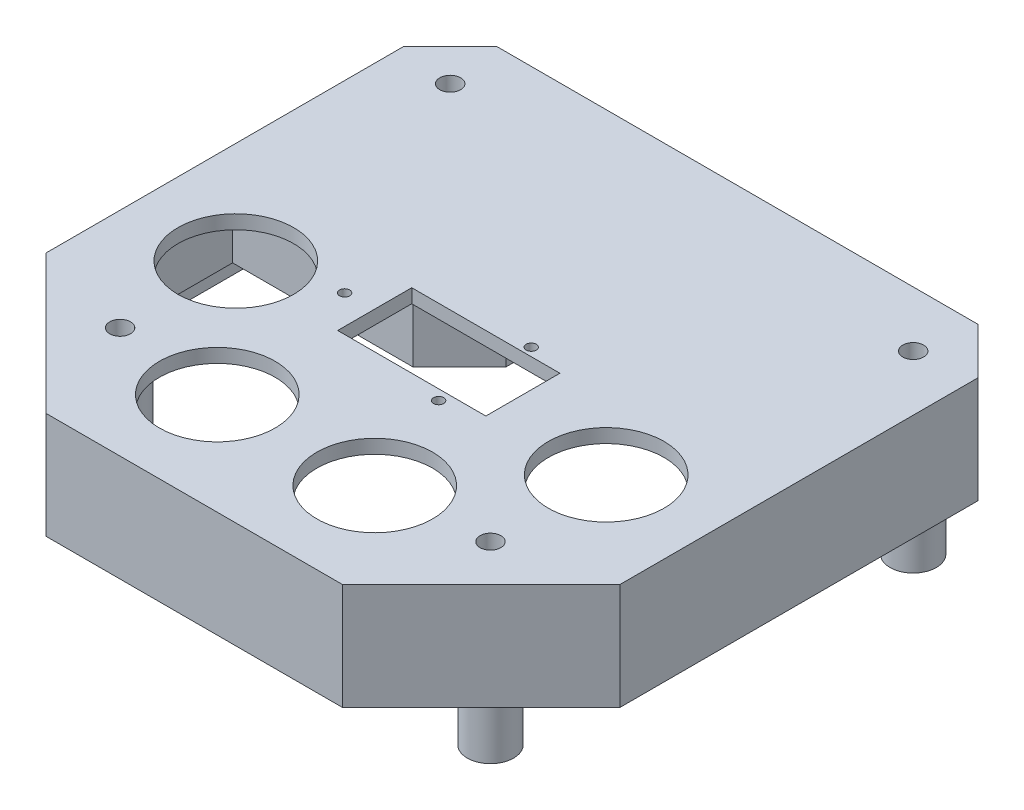
SolidWorks part; units mm, degrees
ref_plane "Plan de face" through (0, 0, 0) normal (0, 0, 1) x (1, 0, 0)
ref_plane "Plan de dessus" through (0, 0, 0) normal (0, 1, 0) x (1, 0, 0)
ref_plane "Plan de droite" through (0, 0, 0) normal (1, 0, 0) x (0, 0, -1)
sketch "Esquisse1" plane through (0, 0, 0) normal (0, 1, 0) x (1, 0, 0)
  line L0 (0, 0) -> (0, 64.9796) construction
  line L1 (-40, 27) -> (0, 27) construction
  line L2 (-17, 0) -> (0, 0) construction
  line L4 (62, -22) -> (-62, -22)
  line L5 (-16, 41) -> (16, 41)
  line L6 (-16, 41) -> (-16, 25)
  line L7 (-16, 25) -> (16, 25)
  line L8 (16, 41) -> (16, 25)
  line L9 (62, -22) -> (62, 95.3055)
  line L10 (62, 95.3055) -> (-62, 95.3055)
  line L11 (-62, -22) -> (-62, 95.3055)
  circle A0 centre (-40, 27) radius 12.5
  circle A1 centre (-17, 0) radius 12.5
  circle A2 centre (17, 0) radius 12.5
  circle A3 centre (40, 27) radius 12.5
  point P15 (0, 25)
  dimension "D1" = 25
  dimension "D2" = 16
  dimension "D3" = 32
  dimension "D4" = 17
  dimension "D5" = 25
  dimension "D6" = 27
  dimension "D7" = 40
  dimension "D8" = 22
  dimension "D9" = 22
  dimension "D10" = 22
sketch "Esquisse3" plane through (0, 0, 0) normal (0, 1, 0) x (1, 0, 0)
  line L0 (9.021, 32.7832) -> (18.021, 32.7832) construction
  line L1 (-22.279, 22.7832) -> (18.021, 22.7832)
  line L2 (-22.279, 22.7832) -> (-22.279, 42.7832)
  line L3 (-22.279, 42.7832) -> (18.021, 42.7832)
  line L4 (18.021, 22.7832) -> (18.021, 42.7832)
  line L5 (-15.079, 26.1832) -> (15.021, 26.1832)
  line L6 (-15.079, 26.1832) -> (-15.079, 40.2832)
  line L7 (-15.079, 40.2832) -> (15.021, 40.2832)
  line L8 (15.021, 26.1832) -> (15.021, 40.2832)
  line L9 (18.021, 38.8332) -> (9.021, 38.8332)
  line L10 (18.021, 38.8332) -> (18.021, 26.7332)
  line L11 (18.021, 26.7332) -> (9.021, 26.7332)
  line L12 (9.021, 38.8332) -> (9.021, 26.7332)
  line L13 (-18.279, 32.7832) -> (-22.279, 32.7832) construction
  line L14 (-9.079, 39.1832) -> (-18.279, 39.1832)
  line L15 (-9.079, 39.1832) -> (-9.079, 26.3832)
  line L16 (-9.079, 26.3832) -> (-18.279, 26.3832)
  line L17 (-18.279, 39.1832) -> (-18.279, 26.3832)
  circle A0 centre (18.021, 32.7832) radius 2.05
  circle A1 centre (8.021, 42.7832) radius 2.05
  circle A2 centre (8.021, 22.7832) radius 2.05
  circle A3 centre (-12.279, 22.7832) radius 2.05
  circle A4 centre (-12.279, 42.7832) radius 2.05
  circle A5 centre (-22.279, 32.7832) radius 2.05
  circle A6 centre (-22.279, 32.7832) radius 1.1
  circle A7 centre (8.021, 42.7832) radius 1.1
  circle A8 centre (8.021, 22.7832) radius 1.1
  dimension "D7" = 4.1
  dimension "D10" = 2.2
  dimension "D1" = 20
  dimension "D2" = 40.3
  dimension "D3" = 30.1
  dimension "D4" = 14.1
  dimension "D5" = 3
  dimension "D6" = 2.5
  dimension "D8" = 10
  dimension "D9" = 10
  dimension "D11" = 12.1
  dimension "D12" = 9
  dimension "D13" = 9.2
  dimension "D14" = 12.8
  dimension "D15" = 4
extrude "Boss.-Extru.1" add sketch "Esquisse1" along normal blind 3
extrude "Enlèv. mat.-Extru.1" cut sketch "Esquisse3" along normal through all contours L2 A6 | L2 A6 | L3 A7 | L3 A7 | L1 A8 | L1 A8 region at (8.021, 0, -22.3163) region at (8.021, 0, -23.25) region at (-22.7458, 0, -32.7832) region at (-21.8121, 0, -32.7832) region at (8.021, 0, -42.3163) region at (8.021, 0, -43.25)
chamfer "Chanfrein1" distance 30 angle 45 2 edges at (-62, 1.5, 22) (62, 1.5, 22)
chamfer "Chanfrein2" distance 10 angle 45 2 edges at (62, 1.5, -95.3055) (-62, 1.5, -95.3055)
sketch "Esquisse4" plane through (0, 0, 0) normal (0, 1, 0) x (1, 0, 0)
  line L0 (-62, 85.3055) -> (-62, 8) construction
  line L1 (52, 95.3055) -> (-52, 95.3055) construction
  line L2 (62, 8) -> (62, 85.3055) construction
  line L3 (-32, -22) -> (32, -22) construction
  circle A0 centre (-40, 2) radius 2.25
  circle A1 centre (-40, 2) radius 5
  circle A2 centre (40, 2) radius 2.25
  circle A3 centre (40, 2) radius 5
  circle A4 centre (50, 83.3055) radius 5
  circle A5 centre (50, 83.3055) radius 2.25
  circle A6 centre (-50, 83.3055) radius 2.25
  circle A7 centre (-50, 83.3055) radius 5
  dimension "D1" = 4.5
  dimension "D2" = 10
  dimension "D3" = 12
  dimension "D4" = 12
  dimension "D5" = 12
  dimension "D6" = 24
  dimension "D7" = 22
  dimension "D8" = 22
extrude "Enlèv. mat.-Extru.2" cut sketch "Esquisse4" along normal through all contours A6 | A5 | A2 | A0 region at (-40, 0, -2) region at (40, 0, -2) region at (50, 0, -83.3055) region at (-50, 0, -83.3055)
extrude "Boss.-Extru.2" add sketch "Esquisse4<3>" against normal blind 35
sketch "Esquisse4<3>" plane through (0, 0, 0) normal (0, 1, 0) x (1, 0, 0) same geometry as "Esquisse4"
sketch "Esquisse5" plane through (0, 0, 0) normal (0, 1, 0) x (1, 0, 0)
  line L0 (-62, 85.3055) -> (-52, 95.3055)
  line L1 (-52, 95.3055) -> (52, 95.3055)
  line L2 (52, 95.3055) -> (62, 85.3055)
  line L3 (62, 85.3055) -> (62, 8)
  line L4 (62, 8) -> (32, -22)
  line L5 (32, -22) -> (-32, -22)
  line L6 (-32, -22) -> (-62, 8)
  line L7 (-62, 8) -> (-62, 85.3055)
  line L8 (-58, 83.6486) -> (-50.3431, 91.3055)
  line L9 (-50.3431, 91.3055) -> (50.3431, 91.3055)
  line L10 (50.3431, 91.3055) -> (58, 83.6486)
  line L11 (58, 83.6486) -> (58, 9.6569)
  line L12 (58, 9.6569) -> (30.3431, -18)
  line L13 (30.3431, -18) -> (-30.3431, -18)
  line L14 (-30.3431, -18) -> (-58, 9.6569)
  line L15 (-58, 9.6569) -> (-58, 83.6486)
  line L16 (-60.7, 84.767) -> (-51.4615, 94.0055)
  line L17 (-51.4615, 94.0055) -> (51.4615, 94.0055)
  line L18 (51.4615, 94.0055) -> (60.1722, 85.2948)
  line L19 (60.1722, 85.2948) -> (60.1722, 8.0107)
  line L20 (60.1722, 8.0107) -> (31.4615, -20.7)
  line L21 (31.4615, -20.7) -> (-31.4615, -20.7)
  line L22 (-31.4615, -20.7) -> (-60.7, 8.5385)
  line L23 (-60.7, 8.5385) -> (-60.7, 84.767)
  point P28 (-46.0808, -6.0808)
  dimension "D1" = 4
  dimension "D2" = 4
  dimension "D3" = 4
  dimension "D4" = 4
  dimension "D5" = 4
  dimension "D6" = 4
  dimension "D7" = 4
  dimension "D8" = 4
  dimension "D9" = 1.3
  dimension "D10" = 1.3
  dimension "D11" = 1.3
  dimension "D12" = 1.3
  dimension "D13" = 1.8278
  dimension "D14" = 1.3
  dimension "D15" = 1.3
  dimension "D16" = 1.3
extrude "Boss.-Extru.3" add sketch "Esquisse5" against normal blind 20 contours L7 L6 L5 L4 L3 L2 L1 L0 L22 L23 L16 L17 L18 L19 L20 L21 region at (-56.8793, 0, -90.1848)
extrude "Boss.-Extru.4" add sketch "Esquisse5<3>" against normal blind 15 contours L23 L22 L21 L20 L19 L18 L17 L16 L14 L15 L8 L9 L10 L11 L12 L13 region at (-54.9025, 0, -88.2079)
sketch "Esquisse5<3>" plane through (0, 0, 0) normal (0, 1, 0) x (1, 0, 0) same geometry as "Esquisse5"
sketch "Esquisse6" plane through (0, 0, 0) normal (1, 0, 0) x (0, 0, -1)
  line L0 (59.0555, -20) -> (51.5555, -20)
  line L1 (95.3055, -20) -> (95.3055, 3) construction
  line L2 (9.6569, -15) -> (83.6486, -15) construction
  line L3 (59.0555, -15) -> (59.0555, -20)
  line L4 (8, -20) -> (85.3055, -20) construction
  line L5 (51.5555, -15) -> (51.5555, -20)
  circle A0 centre (55.3055, -15) radius 3.75
  dimension "D1" = 7.5
  dimension "D2" = 40
extrude "Enlèv. mat.-Extru.4" cut sketch "Esquisse6" against normal through all contours A0 | A0 L0 L3 | A0 L5 L0 region at (0, -18.8022, -55.3055) region at (0, -15, -55.3055)
sketch "Esquisse7" plane through (0, 0, 0) normal (0, 0, 1) x (1, 0, 0)
  line L0 (-50.3431, -15) -> (50.3431, -15) construction
  line L2 (-18.25, -15) -> (-18.25, -20)
  line L3 (-52, -20) -> (52, -20) construction
  line L4 (-25.75, -15) -> (-25.75, -20)
  line L5 (-25.75, -20) -> (-18.25, -20)
  line L6 (-62, 3) -> (-62, -20) construction
  circle A0 centre (-22, -15) radius 3.75
  dimension "D1" = 7.5
  dimension "D2" = 40
extrude "Enlèv. mat.-Extru.6" cut sketch "Esquisse7" against normal through all contours A0 L4 L5 L2 | A0 region at (-22, -15, 0) region at (-22, -18.8022, 0)
ref_plane "Plan1" through (18, 0, 0) normal (-1, 0, 0) x (0, 0, 1)
ref_plane "Plan2" through (-20, 0, 0) normal (-1, 0, 0) x (0, 0, 1)
sketch "Esquisse8" plane through (18, 0, 0) normal (-1, 0, 0) x (0, 0, 1)
  line L0 (-91.3055, -10) -> (-84.3055, 0)
  line L1 (-91.3055, -15) -> (-91.3055, 0) construction
  line L2 (-91.3055, 0) -> (-83.6486, 0) construction
  dimension "D1" = 10
  dimension "D2" = 7
rib "Nervure1" sketch "Esquisse8" sketch "Esquisse8" thickness 2 extrusion direction parallel to sketch draft on no parameters "D1"=2
sketch "Esquisse9" plane through (-20, 0, 0) normal (-1, 0, 0) x (0, 0, 1)
  line L0 (-91.3055, -10) -> (-84.3055, 0)
rib "Nervure2" sketch "Esquisse9" sketch "Esquisse9" thickness 2 extrusion direction parallel to sketch draft on no parameters "D1"=2
ref_plane "Plan3" through (0, 0, -51.3055) normal (0, 0, 1) x (1, 0, 0)
sketch "Esquisse10" plane through (0, 0, -51.3055) normal (0, 0, 1) x (1, 0, 0)
  line L0 (58, -10) -> (51, 0)
  line L1 (58, -15) -> (58, 0) construction
  line L2 (58, 0) -> (30.3431, 0) construction
  dimension "D1" = 10
  dimension "D2" = 7
rib "Nervure3" sketch "Esquisse10" sketch "Esquisse10" thickness 2 extrusion direction parallel to sketch draft on no parameters "D1"=2
sketch "Esquisse11" plane through (0, 0, -51.3055) normal (0, 0, 1) x (1, 0, 0)
  line L0 (-58, -10) -> (-51, 0)
  line L1 (-58, -15) -> (-58, 0) construction
  line L2 (-30.3431, 0) -> (-58, 0) construction
  dimension "D1" = 10
  dimension "D2" = 7
rib "Nervure4" sketch "Esquisse11" sketch "Esquisse11" thickness 2 extrusion direction parallel to sketch draft on no parameters "D1"=2
ref_plane "Plan4" through (50, 0, 0) normal (-1, 0, 0) x (0, 0, 1)
sketch "Esquisse12" plane through (50, 0, 0) normal (-1, 0, 0) x (0, 0, 1)
  line L0 (-91.3055, -10) -> (-88.3055, -10)
  line L1 (-88.3055, 0) -> (-88.3055, -35) construction
rib "Nervure5" sketch "Esquisse12" sketch "Esquisse12" thickness 2 extrusion direction parallel to sketch draft on no parameters "D1"=2
ref_plane "Plan5" through (0, 0, -83.3055) normal (0, 0, 1) x (1, 0, 0)
sketch "Esquisse13" plane through (0, 0, -83.3055) normal (0, 0, 1) x (1, 0, 0)
  line L0 (58, -10) -> (55, -10)
  line L1 (55, -35) -> (55, 0) construction
rib "Nervure6" sketch "Esquisse13" sketch "Esquisse13" thickness 2 extrusion direction parallel to sketch draft on no parameters "D1"=2
sketch "Esquisse14" plane through (0, 0, -83.3055) normal (0, 0, 1) x (1, 0, 0)
  line L0 (-58, -10) -> (-55, -10)
  line L1 (-55, 0) -> (-55, -35) construction
rib "Nervure7" sketch "Esquisse14" sketch "Esquisse14" thickness 2 extrusion direction parallel to sketch draft on no parameters "D1"=2
ref_plane "Plan6" through (-50, 0, 0) normal (1, 0, 0) x (0, 0, -1)
sketch "Esquisse15" plane through (-50, 0, 0) normal (1, 0, 0) x (0, 0, -1)
  line L0 (91.3055, -10) -> (88.3055, -10)
rib "Nervure8" sketch "Esquisse15" sketch "Esquisse15" thickness 2 extrusion direction parallel to sketch draft on no parameters "D1"=2
ref_plane "Plan7" through (0, 0, -2) normal (0, 0, -1) x (-1, 0, 0)
sketch "Esquisse16" plane through (0, 0, -2) normal (0, 0, -1) x (-1, 0, 0)
  line L0 (53.3082, -10) -> (45, -10)
  line L1 (45, -35) -> (45, 0) construction
  point P2 (53.3082, -10)
rib "Nervure9" sketch "Esquisse16" sketch "Esquisse16" thickness 2 extrusion direction parallel to sketch draft on no parameters "D1"=2
sketch "Esquisse17" plane through (0, 0, -2) normal (0, 0, -1) x (-1, 0, 0)
  line L0 (-53.8456, -10) -> (-45, -10)
  line L1 (-45, -35) -> (-45, 0) construction
  point P2 (0, 0)
  point P5 (-53.8456, -10)
rib "Nervure11" sketch "Esquisse17" sketch "Esquisse17" thickness 2 extrusion direction parallel to sketch draft on no parameters "D1"=2
ref_plane "Plan8" through (40, 0, 0) normal (-1, 0, 0) x (0, 0, 1)
sketch "Esquisse18" plane through (40, 0, 0) normal (-1, 0, 0) x (0, 0, 1)
  line L0 (3, -10) -> (8.5223, -10)
  line L1 (3, -35) -> (3, 0) construction
rib "Nervure12" sketch "Esquisse18" sketch "Esquisse18" thickness 2 extrusion direction parallel to sketch draft on no parameters "D1"=2
ref_plane "Plan9" through (-40, 0, 0) normal (1, 0, 0) x (0, 0, -1)
sketch "Esquisse19" plane through (-40, 0, 0) normal (1, 0, 0) x (0, 0, -1)
  line L0 (-3, -10) -> (-9.3431, -10)
rib "Nervure13" sketch "Esquisse19" sketch "Esquisse19" thickness 2 extrusion direction parallel to sketch draft on no parameters "D1"=2
ref_plane "Plan10" through (-11, 0, 0) normal (1, 0, 0) x (0, 0, -1)
sketch "Esquisse20" plane through (-11, 0, 0) normal (1, 0, 0) x (0, 0, -1)
  line L0 (91.3055, -15) -> (46.3055, -15)
  line L1 (59.0555, -15) -> (84.767, -15) construction
  line L2 (46.3055, -15) -> (46.3055, 0)
  line L3 (52.3055, 0) -> (82.3055, 0) construction
  line L4 (46.3055, 0) -> (91.3055, 0)
  line L5 (91.3055, 0) -> (91.3055, -15)
  dimension "D1" = 45
extrude "Boss.-Extru.5" add sketch "Esquisse20" along normal blind 2 and the other way blind 1
ref_plane "Plan11" through (0, 0, -46.3055) normal (0, 0, 1) x (1, 0, 0)
sketch "Esquisse21" plane through (0, 0, -46.3055) normal (0, 0, 1) x (1, 0, 0)
  line L0 (-9, -15) -> (-58, -15)
  line L1 (-58, -15) -> (-58, 0)
  line L2 (-58, 0) -> (-9, 0)
  line L3 (-9, 0) -> (-9, -15)
extrude "Boss.-Extru.6" add sketch "Esquisse21" along normal blind 2 and the other way blind 1
chamfer "Chanfrein3" distance 8 angle 45 1 edges at (-12, -7.5, -47.3055)
chamfer "Chanfrein4" distance 10 angle 45 1 edges at (-9, -7.5, -44.3055)
